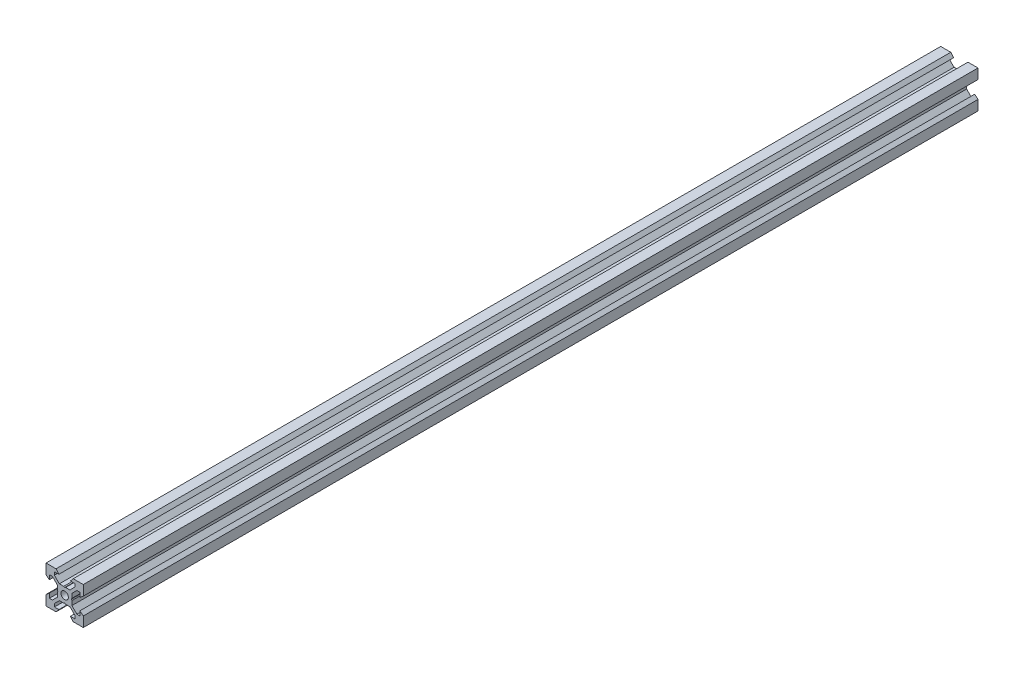
SolidWorks part; units mm, degrees
ref_plane "Front Plane" through (0, 0, 0) normal (0, 0, 1) x (1, 0, 0)
ref_plane "Top Plane" through (0, 0, 0) normal (0, 1, 0) x (1, 0, 0)
ref_plane "Right Plane" through (0, 0, 0) normal (1, 0, 0) x (0, 0, -1)
sketch "Sketch1" plane through (0, 0, 0) normal (0, 0, 1) x (1, 0, 0)
  line L0 (10, 10) -> (4.6104, 10) construction
  line L1 (10, 10) -> (10, 4.6104) construction
  line L2 (10, -10) -> (10, -4.6104) construction
  line L3 (10, -10) -> (4.6104, -10) construction
  line L4 (10, 10) -> (10, 4.6104)
  line L5 (6.5607, 5.5) -> (8.2, 5.5)
  line L6 (5.5, 8.2) -> (5.5, 6.5607)
  line L7 (10, 10) -> (4.6104, 10)
  line L8 (10, 10) -> (10, 4.6104)
  line L9 (6.5607, 5.5) -> (3.9, 2.8393)
  line L10 (5.5, 6.5607) -> (2.8393, 3.9)
  line L11 (10, 4.6104) -> (8.2, 3.1)
  line L12 (4.6104, 10) -> (3.1, 8.2)
  line L13 (8.2, 3.1) -> (8.2, 5.5)
  line L14 (3.1, 8.2) -> (5.5, 8.2)
  line L15 (-6.5607, 5.5) -> (-8.2, 5.5)
  line L16 (6.5607, -5.5) -> (8.2, -5.5)
  line L17 (3.1, -8.2) -> (5.5, -8.2)
  line L18 (8.2, -3.1) -> (8.2, -5.5)
  line L19 (4.6104, -10) -> (3.1, -8.2)
  line L20 (10, -4.6104) -> (8.2, -3.1)
  line L21 (0.5196, -3.9) -> (0, -3.6)
  line L22 (0.5196, 3.9) -> (0, 3.6)
  line L23 (3.6, 0) -> (3.9, -0.5196)
  line L24 (3.9, 0.5196) -> (3.6, 0)
  line L25 (3.9, 0.5196) -> (3.9, 2.8393)
  line L26 (2.8393, 3.9) -> (0.5196, 3.9)
  line L27 (3.9, -2.8393) -> (3.9, -0.5196)
  line L28 (2.8393, -3.9) -> (0.5196, -3.9)
  line L29 (5.5, -6.5607) -> (2.8393, -3.9)
  line L30 (6.5607, -5.5) -> (3.9, -2.8393)
  line L31 (10, -10) -> (10, -4.6104)
  line L32 (10, -10) -> (4.6104, -10)
  line L33 (5.5, -8.2) -> (5.5, -6.5607)
  line L34 (-6.5607, -5.5) -> (-8.2, -5.5)
  line L35 (10, -10) -> (10, -4.6104)
  line L36 (0, 0) -> (0, 8.2) construction
  line L37 (-10, -10) -> (-4.6104, -10) construction
  line L38 (-10, -10) -> (-10, -4.6104) construction
  line L39 (-10, 10) -> (-10, 4.6104) construction
  line L40 (-10, 10) -> (-4.6104, 10) construction
  line L41 (-10, -10) -> (-10, -4.6104)
  line L43 (-5.5, -8.2) -> (-5.5, -6.5607)
  line L44 (-10, -10) -> (-4.6104, -10)
  line L45 (-10, -10) -> (-10, -4.6104)
  line L46 (-6.5607, -5.5) -> (-3.9, -2.8393)
  line L47 (-5.5, -6.5607) -> (-2.8393, -3.9)
  line L48 (-2.8393, -3.9) -> (-0.5196, -3.9)
  line L49 (-3.9, -2.8393) -> (-3.9, -0.5196)
  line L50 (-2.8393, 3.9) -> (-0.5196, 3.9)
  line L51 (-3.9, 0.5196) -> (-3.9, 2.8393)
  line L52 (-3.9, 0.5196) -> (-3.6, 0)
  line L53 (-3.6, 0) -> (-3.9, -0.5196)
  line L54 (-0.5196, 3.9) -> (0, 3.6)
  line L55 (-0.5196, -3.9) -> (0, -3.6)
  line L56 (-10, -4.6104) -> (-8.2, -3.1)
  line L57 (-4.6104, -10) -> (-3.1, -8.2)
  line L58 (-8.2, -3.1) -> (-8.2, -5.5)
  line L59 (-3.1, -8.2) -> (-5.5, -8.2)
  line L60 (-10, -10) -> (10, -10) construction
  line L61 (-10, -10) -> (-10, 10) construction
  line L62 (-3.1, 8.2) -> (-5.5, 8.2)
  line L63 (-8.2, 3.1) -> (-8.2, 5.5)
  line L64 (-4.6104, 10) -> (-3.1, 8.2)
  line L65 (-10, 4.6104) -> (-8.2, 3.1)
  line L66 (-5.5, 6.5607) -> (-2.8393, 3.9)
  line L67 (-6.5607, 5.5) -> (-3.9, 2.8393)
  line L68 (-10, 10) -> (-10, 4.6104)
  line L69 (-10, 10) -> (-4.6104, 10)
  line L70 (-5.5, 8.2) -> (-5.5, 6.5607)
  line L71 (-10, 10) -> (10, 10) construction
  line L72 (-10, 10) -> (-10, 4.6104)
  line L73 (10, -10) -> (10, 10) construction
  line L74 (-10, -10) -> (10, 10) construction
  line L75 (-10, 10) -> (10, -10) construction
  circle A0 centre (0, 0) radius 2
  dimension "D7" = 4
  dimension "D1" = 20
  dimension "D2" = 5.3896
  dimension "D3" = 4.5
  dimension "D4" = 50
  dimension "D5" = 1.8
  dimension "D6" = 1.5104
  dimension "D8" = 5.5
  dimension "D9" = 120
  dimension "D10" = 0.3
  dimension "D11" = 2.3197
  dimension "D12" = 7.8
  dimension "D13" = 7.8
  dimension "D14" = 1.5
  dimension "D15" = 2.6607
extrude "Boss-Extrude1" add sketch "Sketch1" along normal mid plane 480 contours L70 L62 L64 L69 L68 L65 L63 L15 L67 L51 L52 L53 L49 L46 L34 L58 L56 L41 L44 L57 L59 L43 L47 L48 L55 L21 L28 L29 L33 L17 L19 L32 L31 L20 L18 L16 L30 L27 L23 L24 L25 L9 L5 L13 L11 L4 L7 L12 L14 L6 L10 region at (9.7172, 7.3052, 0)
